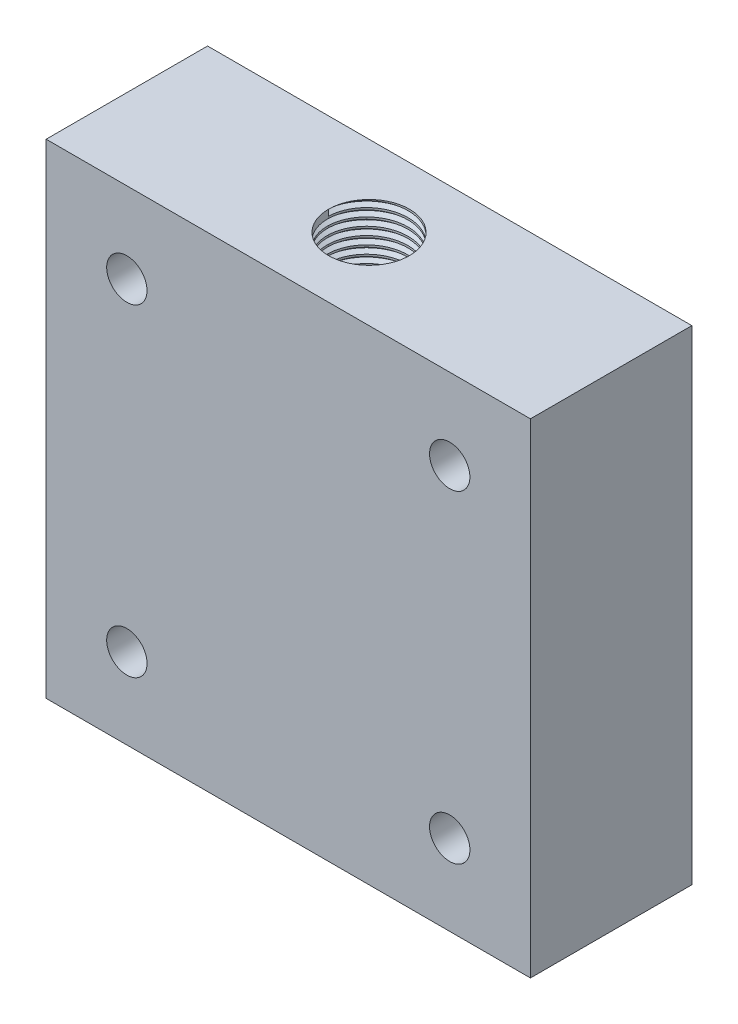
SolidWorks part; units mm, degrees
ref_plane "Front Plane" through (0, 0, 0) normal (0, 0, 1) x (1, 0, 0)
ref_plane "Top Plane" through (0, 0, 0) normal (0, 1, 0) x (1, 0, 0)
ref_plane "Right Plane" through (0, 0, 0) normal (1, 0, 0) x (0, 0, -1)
sketch "Sketch2" plane through (0, 0, 0) normal (0, 0, 1) x (1, 0, 0)
  line L1 (-38.1, -38.1) -> (38.1, -38.1)
  line L2 (-38.1, -38.1) -> (-38.1, 38.1)
  line L3 (-38.1, 38.1) -> (38.1, 38.1)
  line L4 (38.1, -38.1) -> (38.1, 38.1)
  line L5 (-38.1, -38.1) -> (38.1, 38.1) construction
  line L6 (-38.1, 38.1) -> (38.1, -38.1) construction
  point P0 (0, 0)
  dimension "D1" = 76.2
  dimension "D2" = 76.2
extrude "Boss-Extrude1" add sketch "Sketch2" along normal blind 25.4
sketch "Sketch3" plane through (0, 0, 0) normal (0, 0, -1) x (-1, 0, 0)
  circle A0 centre (0, 0) radius 25.4
  circle A1 centre (0, 0) radius 17.4625
  dimension "D1" = 50.8
  dimension "D2" = 34.925
extrude "Cut-Extrude1" cut sketch "Sketch3" against normal blind 3.81
sketch "Sketch5" plane through (0, 38.1, 0) normal (0, 1, 0) x (1, 0, 0)
  line L0 (38.1, 0) -> (-38.1, 0) construction
  circle A0 centre (0, -12.7) radius 6.35
  point P4 (0, 0)
  dimension "D1" = 12.7
  dimension "D2" = 12.7
extrude "Cut-Extrude12" cut sketch "Sketch5" against normal blind 38.1
thread "Thread1" pitch 1.27 method cut profile "Thread Profile2" start angle 0, offset 0, length 12.7, pitch 1.27, diameter 12.7
ref_plane "Plane2" through (-6.35, 38.1, 12.7) normal (0, 0, 1) x (-1, 0, 0)
sketch "Thread Profile2" plane through (-6.35, 38.1, 12.7) normal (0, 0, 1) x (-1, 0, 0)
  line L0 (0, 0) -> (0, 1.27) construction
  line L1 (0, 0) -> (0.6874, 0.3969)
  line L2 (0.6874, 0.3969) -> (0.6874, 0.5556)
  line L3 (0.6874, 0.5556) -> (0, 0.9525)
  line L4 (0.6874, 0.4762) -> (0, 0.4762) construction
  line L11 (0, 0) -> (0, 0.9525)
  point P2 (0, 0)
  dimension "Pitch" = 1.27
  dimension "Profile_Angle" = 60
  dimension "Profile_Land" = 0.1588
  dimension "Profile_Height" = 0.6874
sketch "Sketch25" plane through (0, 0, 0) normal (0, 0, -1) x (-1, 0, 0)
  circle A0 centre (0, 0) radius 12.7
  dimension "D1" = 25.4
extrude "Cut-Extrude15" cut sketch "Sketch25" against normal blind 12.7
sketch "Sketch26" plane through (0, 0, 25.4) normal (0, 0, 1) x (1, 0, 0)
  line L0 (38.1, 38.1) -> (-38.1, 38.1) construction
  line L3 (-38.1, 38.1) -> (-38.1, -38.1) construction
  circle A0 centre (-25.4, 25.4) radius 3.175
  circle A1 centre (25.4, 25.4) radius 3.175
  circle A2 centre (25.4, -25.4) radius 3.175
  circle A3 centre (-25.4, -25.4) radius 3.175
  point P15 (0, 0)
  dimension "D1" = 6.35
  dimension "D2" = 12.7
  dimension "D3" = 12.7
  dimension "D4" = 4
extrude "Cut-Extrude16" cut sketch "Sketch26" against normal through all
chamfer "Chamfer1" distance 2.54 angle 45 1 edges at (-12.7, 0, 0)
chamfer "Chamfer2" distance 1.27 angle 45 1 edges at (-25.4, 0, 0)
fillet "Fillet1" radius 1.27 1 edges at (-17.4625, 0, 3.81)
equation "\"D2@Sketch3\"=1+3/8"
